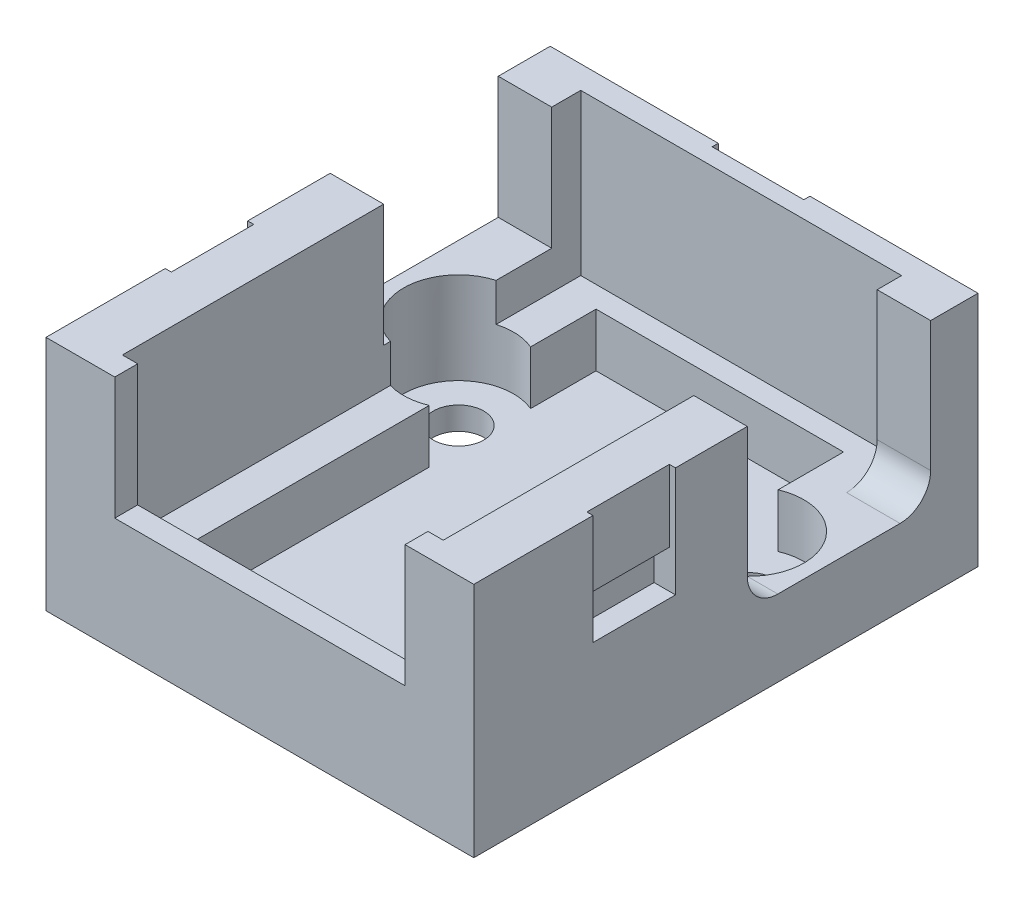
SolidWorks part; units mm, degrees
ref_plane "Płaszczyzna przednia" through (0, 0, 0) normal (0, 0, 1) x (1, 0, 0)
ref_plane "Płaszczyzna górna" through (0, 0, 0) normal (0, 1, 0) x (1, 0, 0)
ref_plane "Płaszczyzna prawa" through (0, 0, 0) normal (1, 0, 0) x (0, 0, -1)
sketch "Szkic1" plane through (0, 0, 0) normal (0, 1, 0) x (1, 0, 0)
  line L1 (-14, -16.5) -> (14, -16.5)
  line L2 (-14, -16.5) -> (-14, 16.5)
  line L3 (-14, 16.5) -> (14, 16.5)
  line L4 (14, -16.5) -> (14, 16.5)
  line L5 (-14, -16.5) -> (14, 16.5) construction
  line L6 (-14, 16.5) -> (14, -16.5) construction
  point P0 (0, 0)
  dimension "D1" = 28
  dimension "D2" = 33
extrude "Dodanie-wyciągnięcie1" add sketch "Szkic1" along normal blind 1.5
sketch "Szkic2" plane through (0, 1.5, 0) normal (0, 1, 0) x (1, 0, 0)
  line L0 (-14, 16.5) -> (14, 16.5)
  line L1 (14, 16.5) -> (14, -16.5)
  line L2 (14, -16.5) -> (-14, -16.5)
  line L3 (-14, -16.5) -> (-14, 16.5)
  line L5 (-10.5, -15) -> (10.5, -15)
  line L6 (-10.5, -15) -> (-10.5, 15)
  line L7 (-10.5, 15) -> (10.5, 15)
  line L8 (10.5, -15) -> (10.5, 15)
  line L9 (-10.5, -15) -> (10.5, 15) construction
  line L10 (-10.5, 15) -> (10.5, -15) construction
  point P4 (0, 0)
  dimension "D1" = 1.5
  dimension "D2" = 3.5
  dimension "D3" = 3.5
  dimension "D4" = 1.5
extrude "Dodanie-wyciągnięcie2" add sketch "Szkic2" along normal blind 14
sketch "Szkic7" plane through (0, 1.5, 0) normal (0, 1, 0) x (1, 0, 0)
  line L1 (-10.5, -15) -> (10.5, -15)
  line L2 (-10.5, -15) -> (-10.5, 15)
  line L3 (-10.5, 15) -> (10.5, 15)
  line L4 (10.5, -15) -> (10.5, 15)
  line L5 (-10.5, -15) -> (10.5, 15) construction
  line L6 (-10.5, 15) -> (10.5, -15) construction
  line L7 (-8.1, -13.6) -> (8.1, -13.6)
  line L8 (-8.1, -13.6) -> (-8.1, 13.6)
  line L9 (-8.1, 13.6) -> (8.1, 13.6)
  line L10 (8.1, -13.6) -> (8.1, 13.6)
  line L11 (-8.1, -13.6) -> (8.1, 13.6) construction
  line L12 (-8.1, 13.6) -> (8.1, -13.6) construction
  point P0 (0, 0)
  point P7 (0, 0)
  dimension "D1" = 1.4
  dimension "D2" = 2.4
extrude "Dodanie-wyciągnięcie4" add sketch "Szkic7" along normal blind 3.5
sketch "Szkic3" plane through (14, 0, 0) normal (1, 0, 0) x (0, 0, -1)
  line L0 (16.5, 0) -> (16.5, 5) construction
  line L1 (16.5, 15.5) -> (16.5, 0) construction
  line L2 (16.5, 5) -> (13.4, 5) construction
  line L3 (13.4, 5) -> (1.4, 5)
  line L4 (1.4, 5) -> (1.4, 15.5)
  line L5 (-16.5, 15.5) -> (16.5, 15.5) construction
  line L6 (1.4, 15.5) -> (13.4, 15.5)
  line L7 (13.4, 15.5) -> (13.4, 5)
  dimension "D1" = 3.1
  dimension "D2" = 12
  dimension "D3" = 5
extrude "Wytnij-wyciągnięcie1" cut sketch "Szkic3" against normal up to surface (3.5 mm away) contours L3 L4 L6 L7 up to face at (10.5, 10.25, 0)
sketch "Szkic4" plane through (0, 0, 16.5) normal (0, 0, 1) x (1, 0, 0)
  line L0 (14, 0) -> (14, 7.5) construction
  line L1 (-14, 0) -> (14, 0) construction
  line L2 (14, 15.5) -> (14, 0) construction
  line L3 (14, 7.5) -> (9.5, 7.5) construction
  line L4 (9.5, 7.5) -> (9.5, 15.5)
  line L5 (-14, 15.5) -> (14, 15.5) construction
  line L6 (9.5, 15.5) -> (-9.5, 15.5)
  line L7 (-9.5, 15.5) -> (-9.5, 7.5)
  line L8 (-9.5, 7.5) -> (9.5, 7.5)
  line L9 (-14, 15.5) -> (-14, 0) construction
  dimension "D1" = 4.5
  dimension "D2" = 4.5
  dimension "D3" = 7.5
extrude "Wytnij-wyciągnięcie2" cut sketch "Szkic4" against normal up to surface (1.5 mm away) up to face at (0, 10.25, 15)
sketch "Szkic5" plane through (-14, 0, 0) normal (-1, 0, 0) x (0, 0, 1)
  line L0 (-16.5, 0) -> (-16.5, 7.5) construction
  line L1 (-16.5, 0) -> (16.5, 0) construction
  line L2 (-16.5, 15.5) -> (-16.5, 0) construction
  line L3 (-16.5, 7.5) -> (-13.1, 7.5) construction
  line L4 (-13.1, 7.5) -> (-13.1, 15.5)
  line L5 (-13.1, 15.5) -> (-2.1, 15.5)
  line L6 (-2.1, 15.5) -> (-2.1, 7.5)
  line L7 (-2.1, 7.5) -> (-13.1, 7.5)
  line L8 (-16.5, 15.5) -> (16.5, 15.5) construction
  dimension "D1" = 3.4
  dimension "D2" = 7.5
  dimension "D3" = 11
extrude "Wytnij-wyciągnięcie3" cut sketch "Szkic5" against normal up to surface (3.5 mm away) up to face at (-10.5, 10.25, 0)
sketch "Szkic8" plane through (0, 0, 0) normal (0, -1, 0) x (1, 0, 0)
  line L0 (0, 0) -> (0, -6) construction
  line L1 (-9.5, -6) -> (9.5, -6) construction
  circle A0 centre (9.5, -6) radius 1.65
  circle A1 centre (-9.5, -6) radius 1.65
  point P6 (0, -6)
  dimension "D3" = 3.3
  dimension "D1" = 6
  dimension "D2" = 19
extrude "Wytnij-wyciągnięcie4" cut sketch "Szkic8" against normal through all
sketch "Szkic9" plane through (0, 0, 0) normal (0, -1, 0) x (1, 0, 0)
  line L0 (0, 0) -> (0, -4.7269) construction
  circle A0 centre (-9.5, -6) radius 3.6
  circle A1 centre (9.5, -6) radius 3.6
  dimension "D1" = 7.2
extrude "Wytnij-wyciągnięcie8" cut sketch "Szkic9" against normal through all from surface starting at face at (0, 1.5, -3)
fillet "Zaokrąglenie1" radius 2 2 edges at (12.25, 5, -1.4) (12.25, 5, -13.4)
sketch "Szkic10" plane through (14, 0, 0) normal (1, 0, 0) x (0, 0, -1)
  line L0 (-16.5, 15.5) -> (-8.7, 15.5) construction
  line L1 (-16.5, 15.5) -> (1.4, 15.5) construction
  line L2 (-8.7, 15.5) -> (-8.7, 8.3)
  line L3 (-8.7, 8.3) -> (-3.3, 8.3)
  line L4 (-3.3, 8.3) -> (-3.3, 15.5)
  line L5 (-3.3, 15.5) -> (-8.7, 15.5)
  dimension "D1" = 7.2
  dimension "D2" = 7.8
  dimension "D3" = 5.4
extrude "Wytnij-wyciągnięcie9" cut sketch "Szkic10" against normal blind 0.4
sketch "Szkic11" plane through (13.6, 0, 0) normal (1, 0, 0) x (0, 0, -1)
  line L0 (-3.3, 8.3) -> (-3.3, 15.5) construction
  line L1 (-8.7, 8.3) -> (-3.3, 8.3)
  line L2 (-8.7, 8.3) -> (-8.7, 10.8)
  line L3 (-8.7, 10.8) -> (-3.3, 10.8)
  line L4 (-3.3, 8.3) -> (-3.3, 10.8)
  line L5 (-8.7, 8.3) -> (-3.3, 10.8) construction
  line L6 (-8.7, 10.8) -> (-3.3, 8.3) construction
  point P4 (-6, 9.55)
  dimension "D1" = 2.5
extrude "Wytnij-wyciągnięcie10" cut sketch "Szkic11" against normal blind 1
sketch "Szkic12" plane through (0, 0, -16.5) normal (0, 0, -1) x (-1, 0, 0)
  line L0 (-3, 15.5) -> (3, 15.5)
  line L2 (-14, 15.5) -> (14, 15.5) construction
  line L3 (3, 15.5) -> (3, 8.3)
  line L4 (3, 8.3) -> (-3, 8.3)
  line L5 (-3, 8.3) -> (-3, 15.5)
  point P5 (0, 15.5)
  point P7 (0, 15.5)
  dimension "D1" = 6
  dimension "D2" = 7.2
extrude "Wytnij-wyciągnięcie11" cut sketch "Szkic12" against normal blind 0.4
sketch "Szkic13" plane through (0, 0, -16.1) normal (0, 0, -1) x (-1, 0, 0)
  line L0 (3, 8.3) -> (3, 15.5) construction
  line L1 (-3, 8.3) -> (3, 8.3)
  line L2 (-3, 8.3) -> (-3, 10.8)
  line L3 (-3, 10.8) -> (3, 10.8)
  line L4 (3, 8.3) -> (3, 10.8)
  line L5 (-3, 8.3) -> (3, 10.8) construction
  line L6 (-3, 10.8) -> (3, 8.3) construction
  point P4 (0, 9.55)
  dimension "D1" = 2.5
extrude "Wytnij-wyciągnięcie12" cut sketch "Szkic13" against normal blind 1
mirror "Lustro1" about plane through (0, 0, 0) normal (1, 0, 0) of "Wytnij-wyciągnięcie10", "Wytnij-wyciągnięcie9"
chamfer "Sfazowanie1" distance 1 angle 45 3 edges at (12.6, 10.8, 6) (0, 10.8, -15.1) (-12.6, 10.8, 6)
